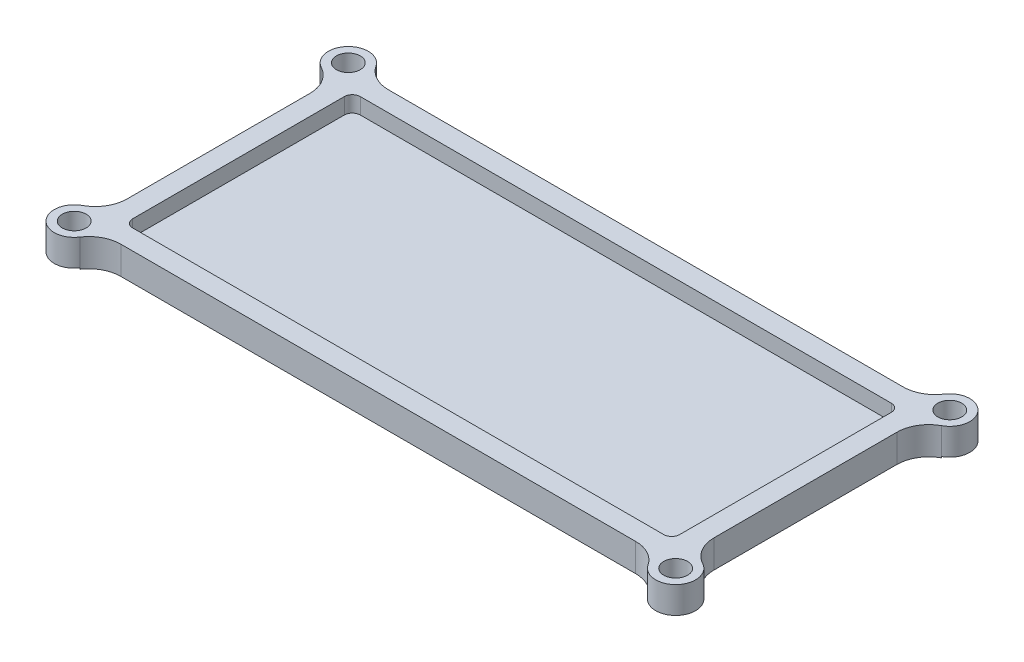
SolidWorks part; units mm, degrees
ref_plane "Front Plane" through (0, 0, 0) normal (0, 0, 1) x (1, 0, 0)
ref_plane "Top Plane" through (0, 0, 0) normal (0, 1, 0) x (1, 0, 0)
ref_plane "Right Plane" through (0, 0, 0) normal (1, 0, 0) x (0, 0, -1)
sketch "Sketch1" plane through (0, 0, 0) normal (0, 1, 0) x (1, 0, 0)
  line L0 (-35.25, 15.25) -> (-36.75, 15.25) construction
  line L1 (35.25, 15.25) -> (-35.25, 15.25)
  line L2 (35.25, 15.25) -> (35.25, -15.25)
  line L3 (35.25, -15.25) -> (-35.25, -15.25)
  line L4 (-35.25, 15.25) -> (-35.25, -15.25)
  line L5 (35.25, 15.25) -> (-35.25, -15.25) construction
  line L6 (35.25, -15.25) -> (-35.25, 15.25) construction
  line L7 (36.75, 16.75) -> (-36.75, 16.75)
  line L8 (36.75, 16.75) -> (36.75, -16.75)
  line L9 (36.75, -16.75) -> (-36.75, -16.75)
  line L10 (-36.75, 16.75) -> (-36.75, -16.75)
  line L11 (36.75, 16.75) -> (-36.75, -16.75) construction
  line L12 (36.75, -16.75) -> (-36.75, 16.75) construction
  line L13 (-35.25, 15.25) -> (-35.25, 16.75) construction
  line L14 (0, 16.75) -> (0, -16.75) construction
  line L15 (-36.75, 0) -> (36.5, 0) construction
  line L16 (-38.6599, 17.1647) -> (-40.1599, 17.1647) construction
  circle A0 centre (-37.6599, 17.1647) radius 1
  circle A1 centre (-37.6599, 17.1647) radius 2.5
  circle A2 centre (37.6599, 17.1647) radius 2.5
  circle A3 centre (37.6599, 17.1647) radius 1
  circle A4 centre (37.6599, -17.1647) radius 1
  circle A5 centre (37.6599, -17.1647) radius 2.5
  circle A6 centre (-37.6599, -17.1647) radius 2.5
  circle A7 centre (-37.6599, -17.1647) radius 1
  point P0 (0, 0)
  point P6 (0, 0)
  dimension "D4" = 2
  dimension "D1" = 30.5
  dimension "D2" = 70.5
  dimension "D3" = 1.5
extrude "Boss-Extrude1" add sketch "Sketch1" along normal blind 1.5 contours L1 L4 L3 L2 | L10 A6 L9 A5 L8 A2 L7 A1 L4 L1 L2 L3 | L10 A1 L7 | L7 A1 L10 A0 | L9 A7 L10 A6 | A6 L10 L9 | L8 A5 L9 | L9 A5 L8 A4 | A2 L8 L7 | L7 A3 L8 A2 region at (0, 0, 0) region at (36.1352, 0, -16.0049) region at (35.9723, 0, -16.8207) region at (35.6572, 0, -15.537) region at (-36.1352, 0, -16.0049) region at (-35.9723, 0, -16.8207) region at (39.0299, 0, 15.1586) region at (36.1352, 0, 16.0049) region at (-36.1352, 0, 16.0049) region at (-36.8207, 0, 15.7931)
sketch "Sketch2" plane through (0, 1.5, 0) normal (0, 1, 0) x (1, 0, 0)
  line L0 (34.25, -14.25) -> (34.25, 14.25)
  line L1 (34.25, 14.25) -> (-34.25, 14.25)
  line L2 (-34.25, 14.25) -> (-34.25, -14.25)
  line L3 (-34.25, -14.25) -> (34.25, -14.25)
  line L4 (36.75, -14.8362) -> (36.75, 14.8362)
  line L5 (35.1946, 16.75) -> (-35.1946, 16.75)
  line L6 (-36.75, 14.8362) -> (-36.75, -14.8362)
  line L7 (-35.1946, -16.75) -> (35.1946, -16.75)
  line L8 (36.75, -14.8362) -> (36.75, 14.8362)
  line L9 (35.1946, 16.75) -> (-35.1946, 16.75)
  line L10 (-36.75, 14.8362) -> (-36.75, -14.8362)
  line L11 (-35.1946, -16.75) -> (35.1946, -16.75)
  arc A0 (34.25, 14.25) -> (34.25, 14.25) centre (34.25, 14.25) ccw
  arc A1 (-34.25, 14.25) -> (-34.25, 14.25) centre (-34.25, 14.25) ccw
  arc A2 (-34.25, -14.25) -> (-34.25, -14.25) centre (-34.25, -14.25) ccw
  arc A3 (34.25, -14.25) -> (34.25, -14.25) centre (34.25, -14.25) ccw
  arc A4 (36.75, 14.8362) -> (35.1946, 16.75) centre (37.6599, 17.1647) ccw
  arc A5 (-35.1946, 16.75) -> (-36.75, 14.8362) centre (-37.6599, 17.1647) ccw
  arc A6 (-36.75, -14.8362) -> (-35.1946, -16.75) centre (-37.6599, -17.1647) ccw
  arc A7 (35.1946, -16.75) -> (36.75, -14.8362) centre (37.6599, -17.1647) ccw
  arc A8 (36.75, 14.8362) -> (35.1946, 16.75) centre (37.6599, 17.1647) ccw
  arc A9 (-35.1946, 16.75) -> (-36.75, 14.8362) centre (-37.6599, 17.1647) ccw
  arc A10 (-36.75, -14.8362) -> (-35.1946, -16.75) centre (-37.6599, -17.1647) ccw
  arc A11 (35.1946, -16.75) -> (36.75, -14.8362) centre (37.6599, -17.1647) ccw
  circle A12 centre (37.6599, -17.1647) radius 1 construction
  circle A13 centre (37.6599, 17.1647) radius 1 construction
  circle A14 centre (-37.6599, 17.1647) radius 1 construction
  circle A15 centre (-37.6599, -17.1647) radius 1 construction
  circle A16 centre (37.6599, -17.1647) radius 1
  circle A17 centre (37.6599, 17.1647) radius 1
  circle A18 centre (-37.6599, 17.1647) radius 1
  circle A19 centre (-37.6599, -17.1647) radius 1
  dimension "D1" = 0
  dimension "D2" = 2.5
extrude "Boss-Extrude2" add sketch "Sketch2" along normal blind 2
fillet "Fillet1" radius 4 8 edges at (36.75, 1.75, -14.8362) (-35.1946, 1.75, -16.75) (36.75, 1.75, 14.8362) (-36.75, 1.75, -14.8362) (35.1946, 1.75, -16.75) (-36.75, 1.75, 14.8362) (35.1946, 1.75, 16.75) (-35.1946, 1.75, 16.75)
hole_wizard "CSK for M2.5 Flat Head Machine Screw1" positions "Sketch5" profile "Sketch6" countersink size "M2.5" standard "ANSI Metric" end condition through all
sketch "Sketch5" plane through (0, 0, 0) normal (0, -1, 0) x (-1, 0, 0)
  point P0 (37.6599, -17.1647)
  point P3 (37.6599, 17.1647)
  point P6 (-37.6599, -17.1647)
  point P9 (-37.6599, 17.1647)
sketch "Sketch6" plane through (-37.6599, 0, 17.1647) normal (1, 0, 0) x (0, 0, -1)
  line L0 (0, 0) -> (0, 3.5)
  line L1 (0, 3.5) -> (1.5, 3.5)
  line L2 (1.5, 3.5) -> (1.5, 1.15)
  line L3 (1.5, 1.15) -> (2.5, 0.15)
  line L4 (2.5, 0.15) -> (2.5, 0)
  line L6 (2.5, 0) -> (0, 0)
  line L7 (-1.5, 1.15) -> (-2.5, 0.15) construction
  line L11 (0, -6.35) -> (0, 107.95) construction
  dimension "Thru Hole Dia." = 3
  dimension "Thru Hole Depth" = 3.5
  dimension "C'Sink Dia." = 5
  dimension "C'Sink Angle" = 90
  dimension "Head Clearance" = 0.15
fillet "Fillet2" radius 1 4 edges at (-34.25, 2.5, 14.25) (34.25, 2.5, 14.25) (-34.25, 2.5, -14.25) (34.25, 2.5, -14.25)
sketch "Sketch10" plane through (0, 3.5, 0) normal (0, 1, 0) x (1, 0, 0)
  line L0 (-32.2381, -16.75) -> (32.2381, -16.75) construction
  line L1 (-31.9, -16.75) -> (-6.1, -16.75)
  line L2 (-31.9, -16.75) -> (-31.9, -15.25)
  line L3 (-31.9, -15.25) -> (-6.1, -15.25)
  line L4 (-6.1, -16.75) -> (-6.1, -15.25)
  line L5 (-35.25, -15.25) -> (-32, -15.25) construction
  line L6 (-32, -15.25) -> (-32, -16.75) construction
  line L7 (-6, -15.25) -> (-6, -16.75) construction
  dimension "D1" = 0.1
  dimension "D2" = 0.1
extrude "Boss-Extrude6" [suppressed] add sketch "Sketch10" along normal blind 1.5
